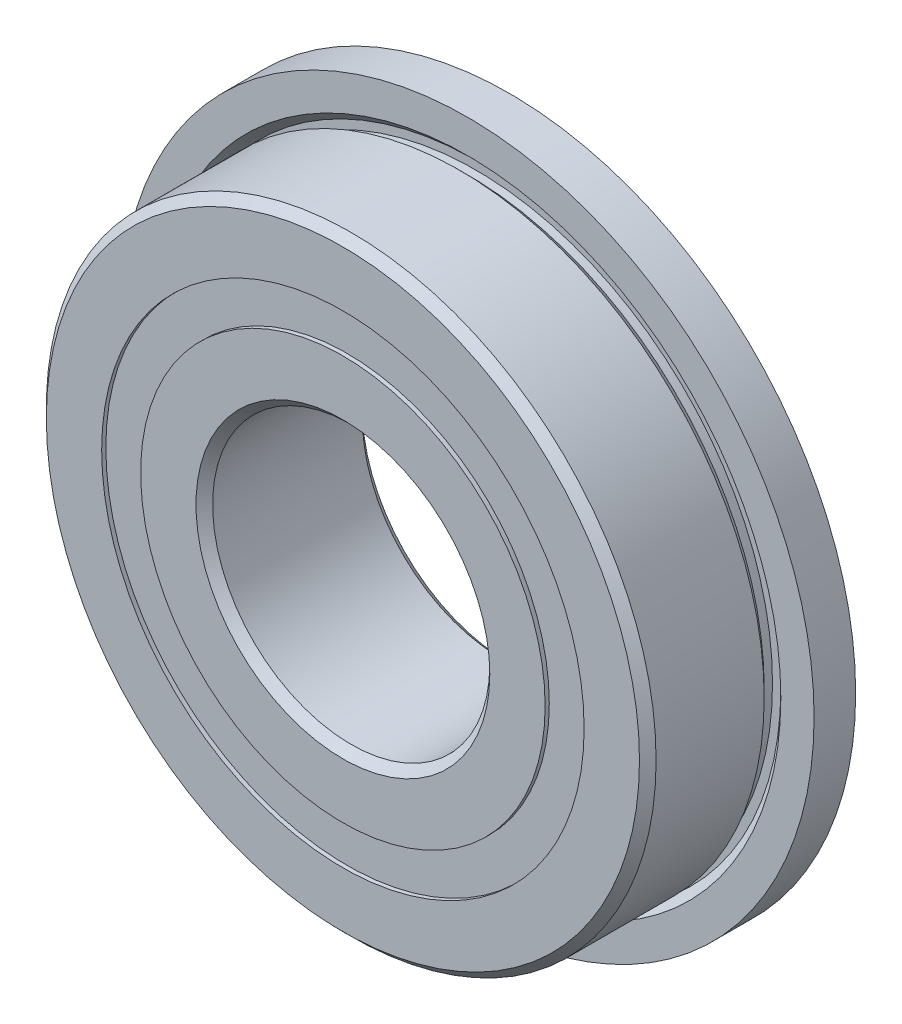
SolidWorks part; units mm, degrees
ref_plane "Front Plane" through (0, 0, 0) normal (0, 0, 1) x (1, 0, 0)
ref_plane "Top Plane" through (0, 0, 0) normal (0, 1, 0) x (1, 0, 0)
ref_plane "Right Plane" through (0, 0, 0) normal (1, 0, 0) x (0, 0, -1)
sketch "Sketch1" plane through (0, 0, 0) normal (0, 0, 1) x (1, 0, 0)
  circle A0 centre (0, 0) radius 5
  dimension "ID" = 10
sketch "Sketch2" plane through (0, 0, 0) normal (1, 0, 0) x (0, 0, -1)
  line L0 (-3, 0) -> (3, 0) construction
  line L1 (0, 11) -> (0, -11) construction
  line L2 (2.7, 11) -> (-2.7, 11) construction
  line L3 (-2.7, 11) -> (-3, 10.7)
  line L4 (-3, 10.7) -> (-3, 8.7033)
  line L5 (-3, 8.7033) -> (-1.3333, 8.7033)
  line L6 (3, 8.7033) -> (1.3333, 8.7033)
  line L7 (3, 10.7) -> (3, 8.7033)
  line L8 (2.7, 11) -> (3, 10.7) construction
  line L9 (0, 11) -> (0, 8) construction
  line L10 (0, 8) -> (0, 5) construction
  line L11 (1.5, 0) -> (1.5, 11) construction
  line L12 (3, 10.7) -> (3, 12.5)
  line L13 (3, 12.5) -> (1.5, 12.5)
  line L14 (1.5, 12.5) -> (1.5, 11.3)
  line L15 (1.5, 11.3) -> (1.8, 11)
  line L16 (1.8, 11) -> (1.8, 10.7)
  line L17 (1.8, 10.7) -> (1.5, 10.7)
  line L18 (1.5, 10.7) -> (1.2, 11)
  line L19 (-2.7, 11) -> (1.2, 11)
  line L20 (3, 12.5) -> (3, -12.5) construction
  line L21 (1.5, 11) -> (1.5, 11.3) construction
  line L22 (1.5, 11) -> (1.2, 11) construction
  line L23 (0, 5) -> (0, -5) construction
  arc A0 (-1.3333, 8.7033) -> (1.3333, 8.7033) centre (0, 8) cw
  point P14 (0, 5)
  point P15 (1.5, 0)
  point P25 (3, 0)
  point P29 (-2.7, -11)
  dimension "D1" = 45
  dimension "D2" = 0.3
  dimension "D3" = 2.6667
  dimension "D4" = 0.7033
  dimension "Flange Thickness" = 1.5
  dimension "Flange OD" = 25
  dimension "Width" = 6
  dimension "OD" = 22
sketch "Sketch7" plane through (0, 0, 0) normal (1, 0, 0) x (0, 0, -1)
  line L13 (3, 12.5) -> (1.5, 12.5)
  line L14 (1.5, 12.5) -> (1.5, 11.3)
  line L15 (1.5, 11.3) -> (1.8, 11)
  line L16 (1.8, 11) -> (1.8, 10.7)
  line L17 (1.8, 10.7) -> (1.5, 10.7)
  line L18 (1.5, 10.7) -> (1.2, 11)
  line L19 (1.2, 11) -> (-2.7, 11)
  line L20 (-2.7, 11) -> (-3, 10.7)
  line L21 (-3, 10.7) -> (-3, 8.7033)
  line L22 (-3, 8.7033) -> (-1.3333, 8.7033)
  line L23 (1.3333, 8.7033) -> (3, 8.7033)
  line L24 (3, 8.7033) -> (3, 10.7)
  line L25 (3, 10.7) -> (3, 12.5)
  line L26 (3, 12.5) -> (1.5, 12.5)
  line L27 (1.5, 12.5) -> (1.5, 11.3)
  line L28 (1.5, 11.3) -> (1.8, 11)
  line L29 (1.8, 11) -> (1.8, 10.7)
  line L30 (1.8, 10.7) -> (1.5, 10.7)
  line L31 (1.5, 10.7) -> (1.2, 11)
  line L32 (1.2, 11) -> (-2.7, 11)
  line L33 (-2.7, 11) -> (-3, 10.7)
  line L34 (-3, 10.7) -> (-3, 8.7033)
  line L35 (-3, 8.7033) -> (-1.3333, 8.7033)
  line L36 (1.3333, 8.7033) -> (3, 8.7033)
  line L37 (3, 8.7033) -> (3, 10.7)
  line L38 (3, 10.7) -> (3, 12.5)
  arc A1 (1.3333, 8.7033) -> (-1.3333, 8.7033) centre (0, 8) ccw
  arc A2 (1.3333, 8.7033) -> (-1.3333, 8.7033) centre (0, 8) ccw
  dimension "D1" = 0
revolve "Revolve7" add sketch "Sketch7" angle 360 about L0
sketch "Sketch3" plane through (0, 0, 0) normal (1, 0, 0) x (0, 0, -1)
  line L0 (-3, 7.2967) -> (-1.3333, 7.2967)
  line L1 (0, 11) -> (0, -11) construction
  line L2 (-3, 10.7) -> (-3, 8.7033) construction
  line L3 (-3, 7.2967) -> (-3, 5.3)
  line L4 (-2.7, 11) -> (-3, 10.7) construction
  line L5 (-3, 5.3) -> (-2.7, 5)
  line L6 (-2.7, 5) -> (2.7, 5)
  line L8 (2.7, 5) -> (3, 5.3)
  line L10 (3, 5.3) -> (3, 7.2967)
  line L11 (3, 7.2967) -> (1.3333, 7.2967)
  line L13 (2.7, 11) -> (3, 10.7) construction
  arc A0 (1.3333, 8.7033) -> (-1.3333, 8.7033) centre (0, 8) ccw construction
  arc A1 (1.3333, 7.2967) -> (-1.3333, 7.2967) centre (0, 8) cw
revolve "Revolve3" add sketch "Sketch3" angle 360 about L0
sketch "Sketch6" plane through (0, 0, 0) normal (1, 0, 0) x (0, 0, -1)
  line L1 (-0.1172, 8.3516) -> (0.1172, 8.3516)
  line L2 (-0.1172, 8.3516) -> (-0.1172, 7.6484)
  line L3 (-0.1172, 7.6484) -> (0.1172, 7.6484)
  line L4 (0.1172, 8.3516) -> (0.1172, 7.6484)
  line L5 (-0.1172, 8.3516) -> (0.1172, 7.6484) construction
  line L6 (-0.1172, 7.6484) -> (0.1172, 8.3516) construction
  point P4 (0, 8)
  dimension "D1" = 0.7033
  dimension "D2" = 0.2344
revolve "Revolve6" add sketch "Sketch6" angle 360 about L0
sketch "Sketch4" plane through (0, 0, 0) normal (1, 0, 0) x (0, 0, -1)
  line L0 (-1.5074, 8) -> (1.5074, 8)
  arc A2 (-1.5074, 8) -> (1.5074, 8) centre (0, 8) cw
  arc A3 (1.3333, 8.7033) -> (-1.3333, 8.7033) centre (0, 8) ccw construction
revolve "Revolve4" add sketch "Sketch4" angle 360 about L0
ref_axis "Axis1" through (0, 0, -3) along (0, 0, 1)
pattern_circular "CirPattern1" count 10 over 360 about axis through (0, 0, -3) along (0, 0, 1) of bodies 104
sketch "Sketch5" plane through (0, 0, 0) normal (1, 0, 0) x (0, 0, -1)
  line L0 (-3, 8.7033) -> (-1.3333, 8.7033) construction
  line L1 (-2.85, 8.7033) -> (-1.5074, 8.7033)
  line L2 (-2.85, 8.7033) -> (-2.85, 7.2967)
  line L3 (-2.85, 7.2967) -> (-1.5074, 7.2967)
  line L4 (-1.5074, 8.7033) -> (-1.5074, 7.2967)
  line L5 (-3, 7.2967) -> (-1.3333, 7.2967) construction
  line L6 (3, 8.7033) -> (1.3333, 8.7033) construction
  line L7 (2.85, 8.7033) -> (1.5074, 8.7033)
  line L8 (2.85, 8.7033) -> (2.85, 7.2967)
  line L9 (2.85, 7.2967) -> (1.5074, 7.2967)
  line L10 (1.5074, 8.7033) -> (1.5074, 7.2967)
  line L11 (3, 7.2967) -> (1.3333, 7.2967) construction
  line L12 (-2.7, 11) -> (-3, 10.7) construction
  point P18 (-2.85, 10.85)
revolve "Revolve5" add sketch "Sketch5" angle 360 about L0
equation "\"D2@Sketch2\" = \"Width@Sketch2\" * .05"
equation "\"D3@Sketch2\" = \"Width@Sketch2\" / 2.25"
equation "\"D4@Sketch2\" =  (  (  ( \"OD@Sketch2\" - \"Width@Sketch2\" )  / 2 )  / 3.25 )  / 3.5"
equation "\"D2@CirPattern1\" = 360/\"Balls@CirPattern1\""
equation "\"D1@Sketch6\" = \"D4@Sketch2\""
equation "\"D2@Sketch6\"=\"D1@Sketch6\"/3"
